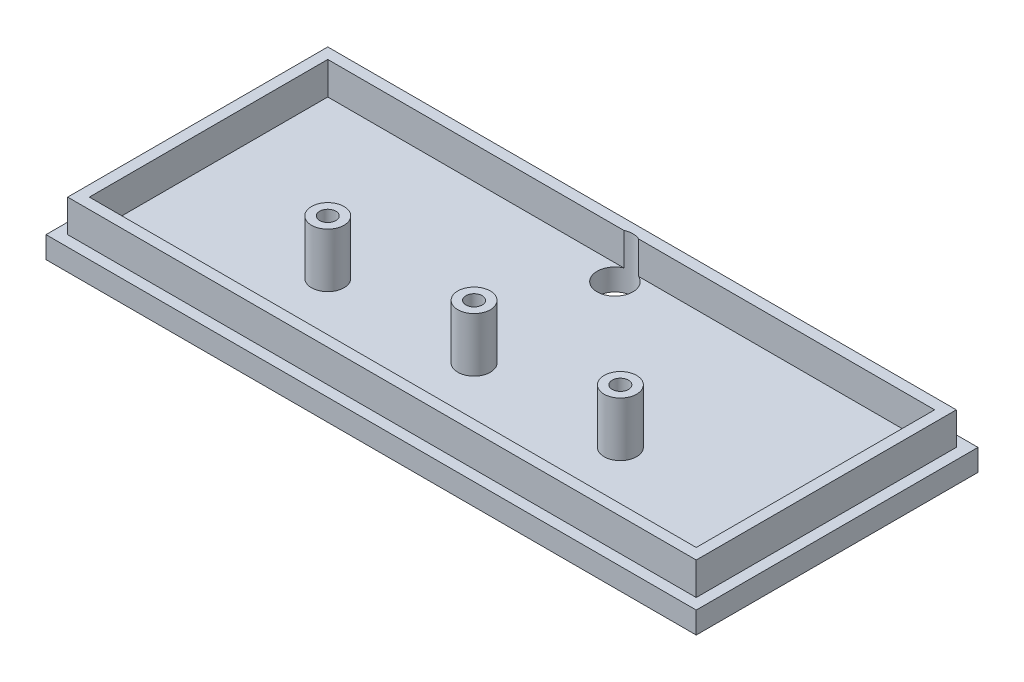
SolidWorks part; units mm, degrees
ref_plane "Front" through (0, 0, 0) normal (0, 0, 1) x (1, 0, 0)
ref_plane "Top" through (0, 0, 0) normal (0, 1, 0) x (1, 0, 0)
ref_plane "Right" through (0, 0, 0) normal (1, 0, 0) x (0, 0, -1)
sketch "Sketch1" plane through (0, 0, 0) normal (0, 1, 0) x (1, 0, 0)
  line L1 (0, 0) -> (60, 0)
  line L2 (0, 0) -> (0, 26)
  line L3 (0, 26) -> (60, 26)
  line L4 (60, 0) -> (60, 26)
  dimension "D1" = 26
  dimension "D2" = 60
extrude "Boss-Extrude1" add sketch "Sketch1" along normal blind 2
sketch "Sketch2" plane through (0, 2, 0) normal (0, 1, 0) x (1, 0, 0)
  line L0 (60, 26) -> (0, 26) construction
  line L1 (1, 25) -> (59, 25)
  line L2 (1, 25) -> (1, 1)
  line L3 (1, 1) -> (59, 1)
  line L4 (59, 25) -> (59, 1)
  line L5 (0, 26) -> (0, 0) construction
  line L6 (0, 0) -> (60, 0) construction
  line L7 (60, 0) -> (60, 26) construction
  line L9 (2, 24) -> (58, 24)
  line L10 (2, 24) -> (2, 2)
  line L11 (2, 2) -> (58, 2)
  line L12 (58, 24) -> (58, 2)
  dimension "D1" = 1
  dimension "D2" = 1
  dimension "D3" = 1
  dimension "D4" = 1
  dimension "D5" = 1
  dimension "D6" = 1
  dimension "D7" = 1
  dimension "D8" = 1
extrude "Boss-Extrude2" add sketch "Sketch2" along normal blind 3
sketch "Sketch3" plane through (0, 2, 0) normal (0, 1, 0) x (1, 0, 0)
  line L0 (2, 24) -> (2, 2) construction
  line L2 (2, 2) -> (58, 2) construction
  circle A0 centre (16.5, 9.5) radius 1.5
  circle A1 centre (30, 9.5) radius 1.5
  circle A2 centre (43.5, 9.5) radius 1.5
  circle A3 centre (16.5, 9.5) radius 0.75
  circle A4 centre (30, 9.5) radius 0.75
  circle A5 centre (43.5, 9.5) radius 0.75
  dimension "D1" = 3
  dimension "D2" = 3
  dimension "D3" = 3
  dimension "D8" = 1.5
  dimension "D9" = 1.5
  dimension "D10" = 1.5
  dimension "D4" = 14.5
  dimension "D5" = 13.5
  dimension "D6" = 13.5
  dimension "D7" = 7.5
extrude "Boss-Extrude3" add sketch "Sketch3" along normal blind 5
hole_wizard "Ø3.3 (3.3) Diameter Hole1" positions "Sketch5" profile "Sketch4" hole size "Ø3.3" standard "ANSI Metric" end condition through all
sketch "Sketch5" plane through (0, 0, 0) normal (0, -1, 0) x (-1, 0, 0)
  line L0 (-60, 26) -> (0, 26) construction
  line L1 (0, 26) -> (0, 0) construction
  point P0 (-30, 22.5)
  dimension "D1" = 3.5
  dimension "D2" = 30
sketch "Sketch4" plane through (30, 0, -22.5) normal (1, 0, 0) x (0, 0, -1)
  line L0 (0, 0) -> (0, 7)
  line L1 (0, 7) -> (1.65, 7)
  line L2 (1.65, 7) -> (1.65, 0)
  line L5 (1.65, 0) -> (0, 0)
  line L11 (0, -6.35) -> (0, 107.95) construction
  dimension "Thru Hole Dia." = 3.3
  dimension "Thru Hole Depth" = 7
